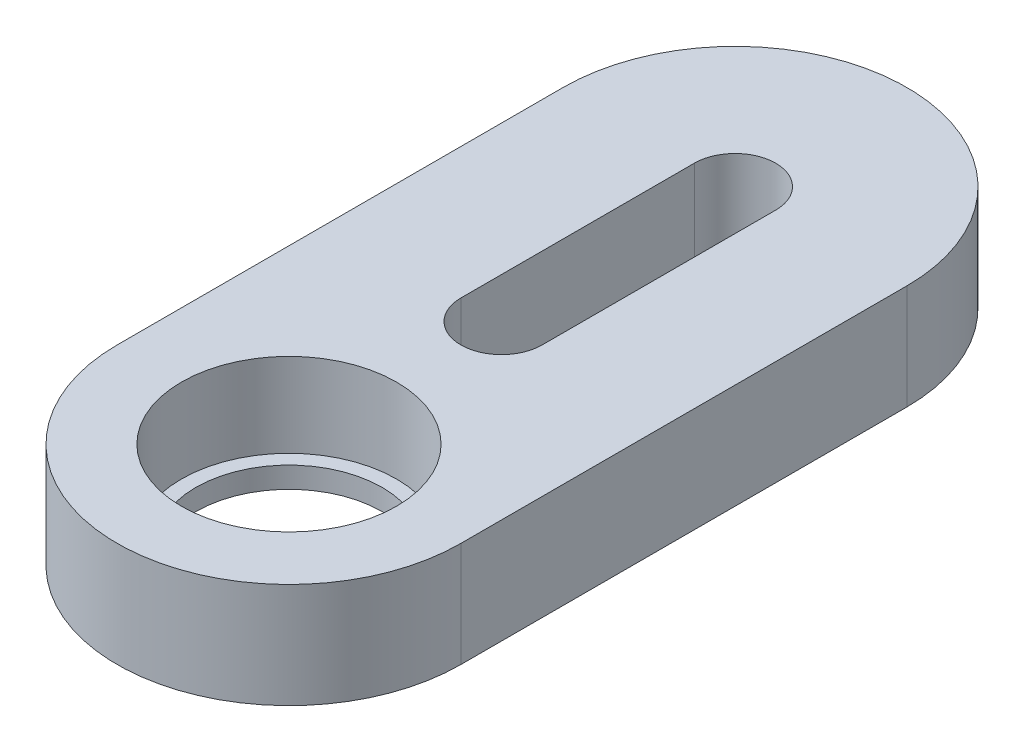
SolidWorks part; units mm, degrees
ref_plane "Front Plane" through (0, 0, 0) normal (0, 0, 1) x (1, 0, 0)
ref_plane "Top Plane" through (0, 0, 0) normal (0, 1, 0) x (1, 0, 0)
ref_plane "Right Plane" through (0, 0, 0) normal (1, 0, 0) x (0, 0, -1)
sketch "Sketch1" plane through (0, 0, 0) normal (0, 1, 0) x (1, 0, 0)
  line L0 (-6.55, 0) -> (-6.55, 17)
  line L1 (6.55, 17) -> (6.55, 0)
  line L2 (0, 17) -> (0, 8.1) construction
  line L3 (1.55, 17) -> (1.55, 8.1)
  line L4 (-1.55, 17) -> (-1.55, 8.1)
  line L5 (0, 18.55) -> (0, 23.55) construction
  line L7 (0, 6.55) -> (0, 4.1) construction
  circle A0 centre (0, 0) radius 4.1
  circle A1 centre (0, 0) radius 6.55
  arc A2 (-6.55, 17) -> (6.55, 17) centre (0, 17) cw
  arc A3 (1.55, 17) -> (-1.55, 17) centre (0, 17) ccw
  arc A4 (-1.55, 8.1) -> (1.55, 8.1) centre (0, 8.1) ccw
  point P8 (0, 12.55)
  point P16 (0, 6.55)
  point P20 (0, 9.3314)
  dimension "D1" = 8.2
  dimension "D2" = 3.1
  dimension "D3" = 5
  dimension "D4" = 12
extrude "Boss-Extrude1" add sketch "Sketch1" along normal blind 4 contours A2 L0 A1 L1 A4 L4 A3 L3 | A1 A0 region at (-4.5005, 0, -4.5005) region at (-6.2805, 0, -8.5)
sketch "Sketch2" plane through (0, 0, 0) normal (0, 1, 0) x (1, 0, 0)
  circle A0 centre (0, 0) radius 4.1
  circle A1 centre (0, 0) radius 4.1 construction
extrude "Boss-Extrude2" add sketch "Sketch2" along normal blind 0.8
sketch "Sketch3" plane through (0, 0.8, 0) normal (0, 1, 0) x (1, 0, 0)
  circle A0 centre (0, 0) radius 3.55
  dimension "D1" = 7.1
extrude "Cut-Extrude1" cut sketch "Sketch3" against normal through all
